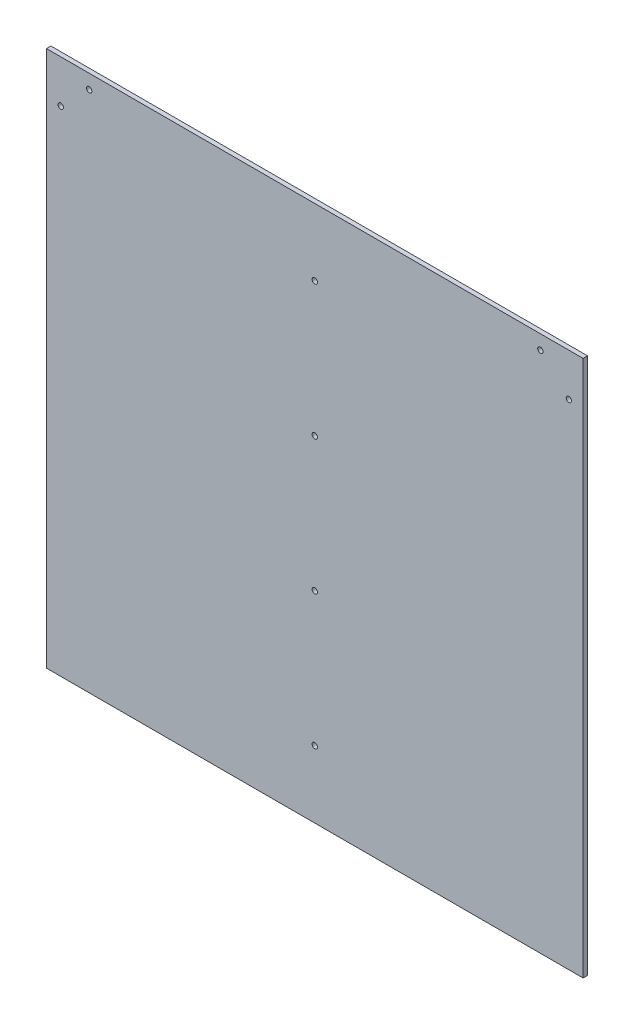
SolidWorks part; units mm, degrees
ref_plane "Front Plane" through (0, 0, 0) normal (0, 0, 1) x (1, 0, 0)
ref_plane "Top Plane" through (0, 0, 0) normal (0, 1, 0) x (1, 0, 0)
ref_plane "Right Plane" through (0, 0, 0) normal (1, 0, 0) x (0, 0, -1)
sketch "Sketch1" plane through (0, 0, 0) normal (0, 0, 1) x (1, 0, 0)
  line L1 (173, 396.7) -> (-227, 396.7)
  line L2 (173, 396.7) -> (173, -3.3)
  line L3 (173, -3.3) -> (-227, -3.3)
  line L4 (-227, 396.7) -> (-227, -3.3)
  line L5 (173, 396.7) -> (-227, -3.3) construction
  line L6 (173, -3.3) -> (-227, 396.7) construction
  point P4 (-27, 196.7)
extrude "Boss-Extrude1" add sketch "Sketch1" along normal blind 3.3
sketch "Sketch2" plane through (0, 0, 3.3) normal (0, 0, 1) x (1, 0, 0)
  line L0 (-227, -3.3) -> (173, -3.3) construction
  line L1 (-54, -3.3) -> (0, -3.3)
  line L2 (-54, -3.3) -> (-54, 396.7)
  line L3 (-54, 396.7) -> (0, 396.7)
  line L4 (0, -3.3) -> (0, 396.7)
  line L5 (-54, -3.3) -> (0, 396.7) construction
  line L6 (-54, 396.7) -> (0, -3.3) construction
  line L7 (173, 396.7) -> (-227, 396.7) construction
  line L8 (0, 393.4) -> (0, 0) construction
  line L9 (-54, 393.4) -> (-54, 0) construction
  line L10 (-27, -3.3) -> (-27, 396.7) construction
  line L11 (-54, 196.7) -> (0, 196.7) construction
  line L12 (162.3934, 364.8802) -> (141.1802, 386.0934) construction
  circle A0 centre (-27, 146.7) radius 2
  circle A1 centre (-27, 46.7) radius 2
  circle A2 centre (-27, 246.7) radius 2
  circle A3 centre (-27, 346.7) radius 2
  circle A4 centre (162.3934, 364.8802) radius 2
  circle A5 centre (141.1802, 386.0934) radius 2
  circle A6 centre (-195.1802, 386.0934) radius 2
  circle A7 centre (-216.3934, 364.8802) radius 2
  point P4 (-27, 196.7)
  point P30 (151.7868, 375.4868)
  point P32 (0, 0)
  point P37 (-27, 196.7)
  dimension "D1" = 50
  dimension "D2" = 150
  dimension "D3" = 4
  dimension "D4" = 4
  dimension "D5" = 4
  dimension "D6" = 4
  dimension "D10" = 21.2132
  dimension "D7" = 30
  dimension "D8" = 45
  dimension "D9" = 30
  dimension "D11" = 2
extrude "Cut-Extrude1" cut sketch "Sketch2" against normal blind 4 contours A4 | A5 | A1 | A0 | A2 | A3 | A6 | A7 region at (162.3934, 364.8802, 3.3) region at (141.1802, 386.0934, 3.3)
